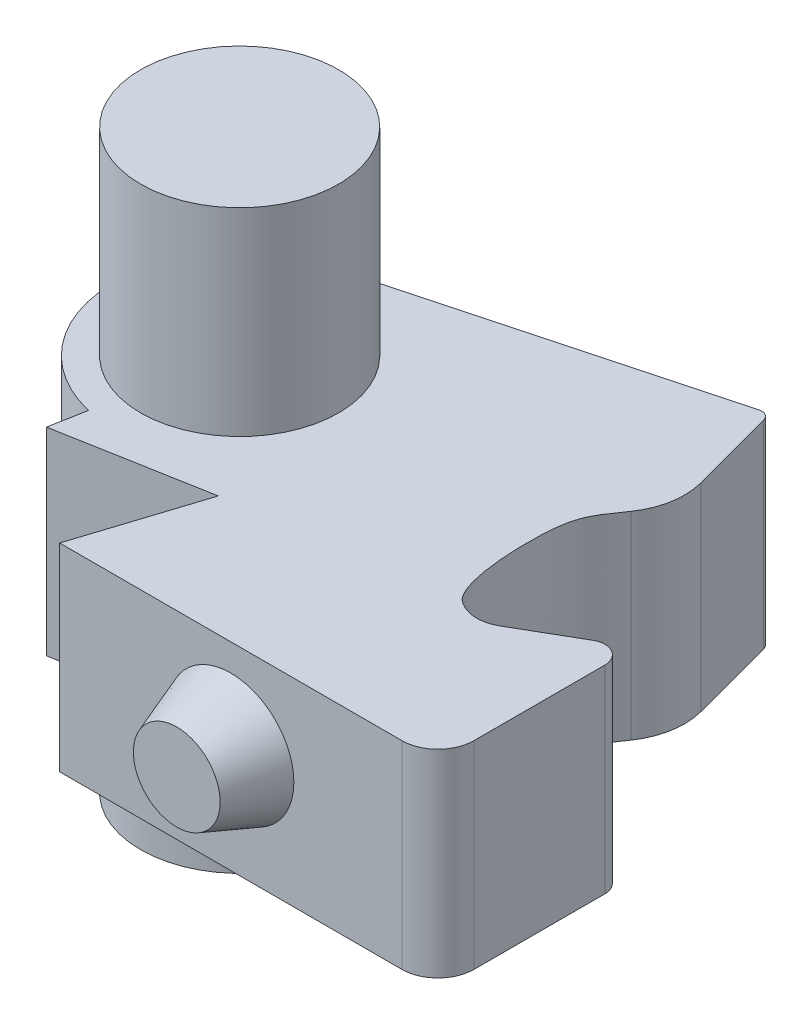
SolidWorks part; units mm, degrees
note: The reader was unsure of these and kept them because the rebuilt part matched: shared geometry of "Sketch1<3>".
ref_plane "Front Plane" through (0, 0, 0) normal (0, 0, 1) x (1, 0, 0)
ref_plane "Top Plane" through (0, 0, 0) normal (0, 1, 0) x (1, 0, 0)
ref_plane "Right Plane" through (0, 0, 0) normal (1, 0, 0) x (0, 0, -1)
sketch "Sketch1" plane through (0, 0, 0) normal (0, 1, 0) x (1, 0, 0)
  line L5 (3.5272, 2.291) -> (3.7828, 1.337)
  line L6 (0, 0) -> (-0.3623, 1.3523) construction
  line L7 (-0.3623, 1.3523) -> (3.4048, 2.3617)
  line L8 (0, 0) -> (1.1, 0) construction
  line L9 (4.7018, -0.7732) -> (4.0416, -1.1543)
  line L11 (0, 0) -> (-0.3855, -1.7579) construction
  line L12 (0.8018, -2.8) -> (1.2296, -1.467)
  line L13 (-1.4, 0) -> (0, 0) construction
  line L14 (0.8018, -2.8) -> (4.6018, -2.8)
  line L15 (5.0018, -2.4) -> (5.0018, -0.9464)
  line L16 (-0.3855, -1.7579) -> (1.2296, -1.467)
  line L18 (-0.3855, -1.7579) -> (-0.3131, -1.3645)
  circle A3 centre (0, 0) radius 1.1
  circle A4 centre (0, 0) radius 1.4
  arc A5 (3.4048, 2.3617) -> (3.5272, 2.291) centre (3.4306, 2.2651) cw
  arc A6 (3.7828, 1.337) -> (3.6681, 0.675) centre (3.0101, 1.13) cw
  arc A7 (5.0018, -0.9464) -> (4.7018, -0.7732) centre (4.8018, -0.9464) ccw
  arc A8 (4.6018, -2.8) -> (5.0018, -2.4) centre (4.6018, -2.4) ccw
  arc A9 (3.5987, -1.1257) -> (4.0416, -1.1543) centre (3.8416, -0.8079) ccw
  spline S0 degree 3 poles (3.6681, 0.675) (3.5078, 0.4432) (3.3379, 0.2716) (3.4163, -0.9863) (3.5987, -1.1257) knots 0.076224 0.076224 0.076224 0.076224 0.275181 0.474138 0.474138 0.474138 0.474138
  point P7 (1.1745, -1.5728)
  point P12 (5.0018, -0.6)
  point P15 (3.5014, 2.3876)
  point P19 (0, 0)
  point P21 (0.8018, -2.8)
  point P24 (1.1685, -1.6574)
  point P27 (0.8018, -2.8)
  point P29 (0.7795, -2.8)
  point P30 (1.1401, -1.5728)
  point P31 (0.8018, -2.8)
  point P33 (-0.3855, -1.7579)
  dimension "D9" = 0.4
  dimension "D14" = 60
  dimension "D12" = 0.1
  dimension "D11" = 2.2
  dimension "D13" = 1.8
  dimension "D6" = 0.8
  dimension "D10" = 0.4
  dimension "D15" = 0.2
  dimension "D16" = 0.4
  dimension "D19" = 3.8
  dimension "D2" = 0.3
  dimension "D3" = 105
  dimension "D4" = 4
  dimension "D5" = 1.4
  dimension "D7" = 180
  dimension "D8" = 2.8
  dimension "D17" = 3.4
  dimension "D18" = 0.8018
extrude "Boss-Extrude1" add sketch "Sketch1" along normal blind 2.2
extrude "Boss-Extrude2" add sketch "Sketch1<3>" along normal blind 4.4 and the other way blind 2
sketch "Sketch1<3>" plane through (0, 0, 0) normal (0, 1, 0) x (1, 0, 0) same geometry as "Sketch1"
sketch "Sketch2" plane through (0, 0, 2.8) normal (0, 0, 1) x (1, 0, 0)
  line L0 (4.6018, 2.2) -> (4.6018, 0) construction
  line L1 (0.8018, 2.2) -> (4.6018, 2.2) construction
  circle A0 centre (2.7018, 1.2) radius 0.7
  dimension "D1" = 1.4
  dimension "D2" = 1.9
  dimension "D3" = 1
extrude "Boss-Extrude3" add sketch "Sketch2" along normal blind 0.6 draft 20
